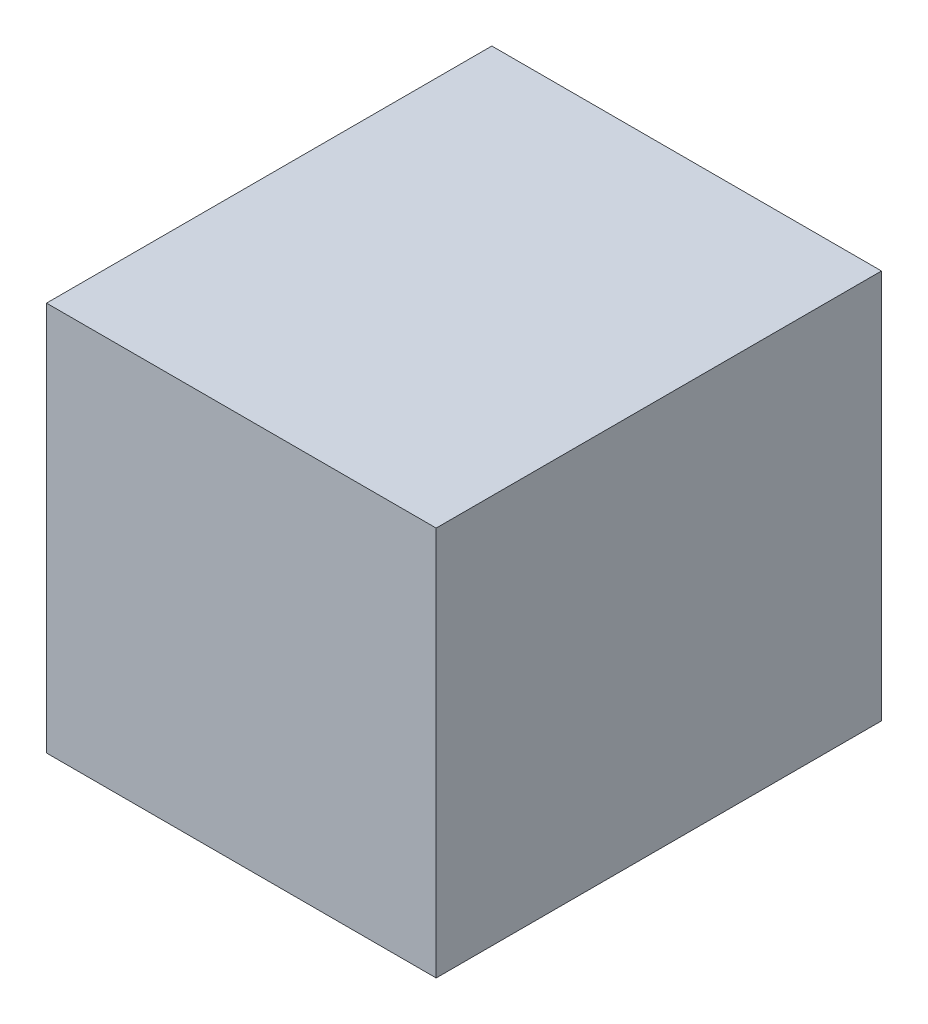
SolidWorks part; units mm, degrees
material "Custom Plastic"
ref_plane "Front Plane" through (0, 0, 0) normal (0, 0, 1) x (1, 0, 0)
ref_plane "Top Plane" through (0, 0, 0) normal (0, 1, 0) x (1, 0, 0)
ref_plane "Right Plane" through (0, 0, 0) normal (1, 0, 0) x (0, 0, -1)
other "Configuration Table"
sketch "Sketch1" plane through (0, 0, 0) normal (0, 0, 1) x (1, 0, 0)
  circle A0 centre (0, 0) radius 10
  dimension "D1" = 20
extrude "Boss-Extrude1" add sketch "Sketch1" along normal mid plane 20
sketch "Sketch2" plane through (0, 0, 0) normal (0, 0, 1) x (1, 0, 0)
  line L1 (-17.5, -17.5) -> (17.5, -17.5)
  line L2 (-17.5, -17.5) -> (-17.5, 17.5)
  line L3 (-17.5, 17.5) -> (17.5, 17.5)
  line L4 (17.5, -17.5) -> (17.5, 17.5)
  line L5 (-17.5, -17.5) -> (17.5, 17.5) construction
  line L6 (-17.5, 17.5) -> (17.5, -17.5) construction
  circle A0 centre (0, 0) radius 15
  dimension "D1" = 30
  dimension "D2" = 35
extrude "Boss-Extrude2" add sketch "Sketch2" along normal mid plane 30 separate body
sketch "Sketch3" plane through (0, 0, 15) normal (0, 0, 1) x (1, 0, 0)
  line L4 (17.5, -17.5) -> (17.5, 17.5)
  line L5 (17.5, 17.5) -> (-17.5, 17.5)
  line L6 (-17.5, 17.5) -> (-17.5, -17.5)
  line L7 (-17.5, -17.5) -> (17.5, -17.5)
  line L8 (17.5, -17.5) -> (17.5, 17.5)
  line L9 (17.5, 17.5) -> (-17.5, 17.5)
  line L10 (-17.5, 17.5) -> (-17.5, -17.5)
  line L11 (-17.5, -17.5) -> (17.5, -17.5)
  dimension "D1" = 0
extrude "Boss-Extrude3" add sketch "Sketch3" along normal blind 5
mirror "Mirror1" about plane through (0, 0, 0) normal (0, 0, 1) of "Boss-Extrude3"
